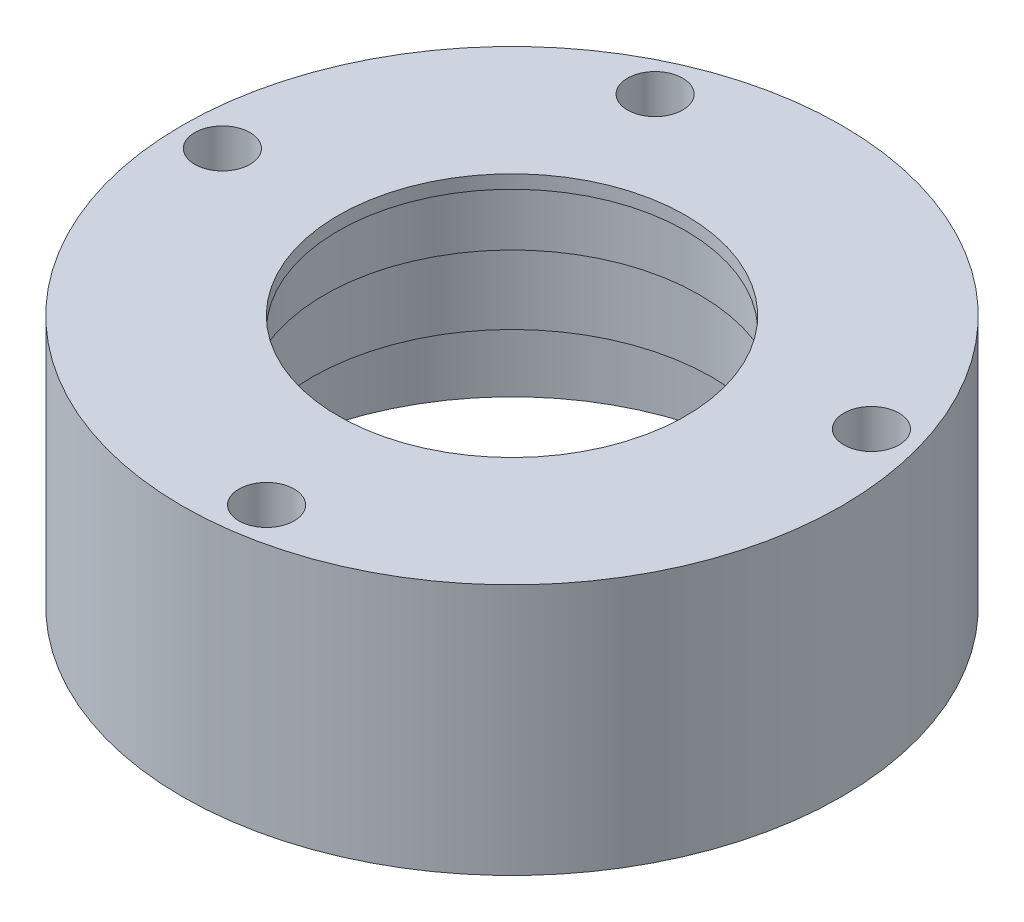
SolidWorks part; units mm, degrees
ref_plane "Front Plane" through (0, 0, 0) normal (0, 0, 1) x (1, 0, 0)
ref_plane "Top Plane" through (0, 0, 0) normal (0, 1, 0) x (1, 0, 0)
ref_plane "Right Plane" through (0, 0, 0) normal (1, 0, 0) x (0, 0, -1)
sketch "Sketch1" plane through (0, 0, 0) normal (0, 1, 0) x (1, 0, 0)
  circle A0 centre (0, 0) radius 37
  dimension "D1" = 74
extrude "Boss-Extrude1" add sketch "Sketch1" along normal blind 28.25
sketch "Sketch2" plane through (0, 0, 0) normal (0, 1, 0) x (1, 0, 0)
  circle A0 centre (0, 0) radius 28.8
  dimension "D1" = 57.6
extrude "Cut-Extrude1" cut sketch "Sketch2" along normal blind 11
sketch "Sketch3" plane through (0, 11, 0) normal (0, -1, 0) x (1, 0, 0)
  circle A0 centre (0, 0) radius 22.5
  dimension "D1" = 45
extrude "Cut-Extrude2" cut sketch "Sketch3" against normal blind 8.75
sketch "Sketch4" plane through (0, 19.75, 0) normal (0, -1, 0) x (1, 0, 0)
  circle A0 centre (0, 0) radius 21.05
  dimension "D1" = 42.1
extrude "Cut-Extrude3" cut sketch "Sketch4" against normal blind 7
sketch "Sketch5" plane through (0, 26.75, 0) normal (0, -1, 0) x (1, 0, 0)
  circle A0 centre (0, 0) radius 19.5
  dimension "D1" = 39
extrude "Cut-Extrude4" cut sketch "Sketch5" against normal through all
sketch "Sketch6" plane through (0, 0, 0) normal (0, 1, 0) x (1, 0, 0)
  line L0 (-15.5375, 0) -> (15.5375, 0) construction
  circle A0 centre (27, 0) radius 1.675
  dimension "D1" = 3.35
  dimension "D2" = 27
extrude "Cut-Extrude5" cut sketch "Sketch6" along normal blind 15.75
pattern_circular "CirPattern1" count 11 over 360 about axis through (0, 28.25, 0) along (0, -1, 0) of "Cut-Extrude5" reverse direction yes
sketch "Sketch7" plane through (0, 0, 0) normal (0, 1, 0) x (1, 0, 0)
  line L0 (0, 0) -> (43.5659, 0) construction
  line L1 (0, 0) -> (39.8091, 11.6863) construction
  line L2 (0, 0) -> (-18.3308, 40.1305) construction
  line L3 (0, 0) -> (-43.804, 0) construction
  line L4 (0, 0) -> (6.4033, -44.546) construction
  circle A0 centre (31.1841, 9.1543) radius 1.7
  circle A1 centre (-13.5033, 29.562) radius 1.7
  circle A2 centre (-32.5, 0) radius 1.7
  circle A3 centre (4.6242, -32.1693) radius 1.7
  dimension "D5" = 3.4
  dimension "D6" = 3.4
  dimension "D7" = 3.4
  dimension "D8" = 3.4
  dimension "D1" = 16.36
  dimension "D2" = 114.55
  dimension "D3" = 180
  dimension "D4" = 278.18
  dimension "D9" = 32.5
  dimension "D10" = 32.5
  dimension "D11" = 32.5
  dimension "D12" = 32.5
extrude "Cut-Extrude6" cut sketch "Sketch7" along normal through all
sketch "Sketch8" plane through (0, 28.25, 0) normal (0, 1, 0) x (1, 0, 0)
  circle A0 centre (31.1841, 9.1543) radius 3.1
  circle A1 centre (-13.5033, 29.562) radius 3.1
  circle A2 centre (-32.5, 0) radius 3.1
  circle A3 centre (4.6242, -32.1693) radius 3.1
  dimension "D1" = 6.2
  dimension "D2" = 6.2
  dimension "D3" = 6.2
  dimension "D4" = 6.2
extrude "Cut-Extrude7" cut sketch "Sketch8" against normal blind 16.25
equation "\"pin_circle_R\" = 27"
equation "\"ecc\" = 1.5"
equation "\"n_pins\" = 11"
equation "\"pin_d\" = 3"
equation "\"out_pin_R\" = 18.5"
equation "\"disc_clr\" = 0.1"
equation "\"seat_6803\" = 26.1"
equation "\"seat_6806\" = 42.1"
equation "\"disc_t\" = 5"
equation "\"out_hole_clr\" = 0.5"
equation "\"boss_17\" = 17.13"
equation "\"rotor_bolt_R\" = 10"
equation "\"m25_clr\" = 2.8"
equation "\"m25_head\" = 5"
equation "\"insert_hole\" = 4.4"
equation "\"csk\" = 0.6"
equation "\"peg_d\" = 3.0"
equation "\"plug_d\" = 8.6"
equation "\"peg_clr\" = 0.3"
equation "\"m3_clr\" = 3.4"
equation "\"m3_head\" = 6.2"
equation "\"pin_press\" = 3.2"
equation "\"pin_slip\" = 3.35"
equation "\"hub_30\" = 30.18"
equation "\"hub_short\" = 0.2"
equation "\"m3_tap\" = 2.8"
equation "\"rear_plate_t\" = 2"
equation "\"motor_ring\" = 40.4"
equation "\"D1@Sketch4\"=\"seat_6806\""
equation "\"D1@Sketch6\"=\"pin_slip\""
equation "\"D2@Sketch6\"=\"pin_circle_R\""
equation "\"D1@CirPattern1\"=\"n_pins\""
equation "\"D5@Sketch7\"=\"m3_clr\""
equation "\"D6@Sketch7\"=\"m3_clr\""
equation "\"D7@Sketch7\"=\"m3_clr\""
equation "\"D8@Sketch7\"=\"m3_clr\""
equation "\"D1@Sketch8\"=\"m3_head\""
equation "\"D2@Sketch8\"=\"m3_head\""
equation "\"D3@Sketch8\"=\"m3_head\""
equation "\"D4@Sketch8\"=\"m3_head\""
equation "\"plug_shaft_d\" = 8.8"
